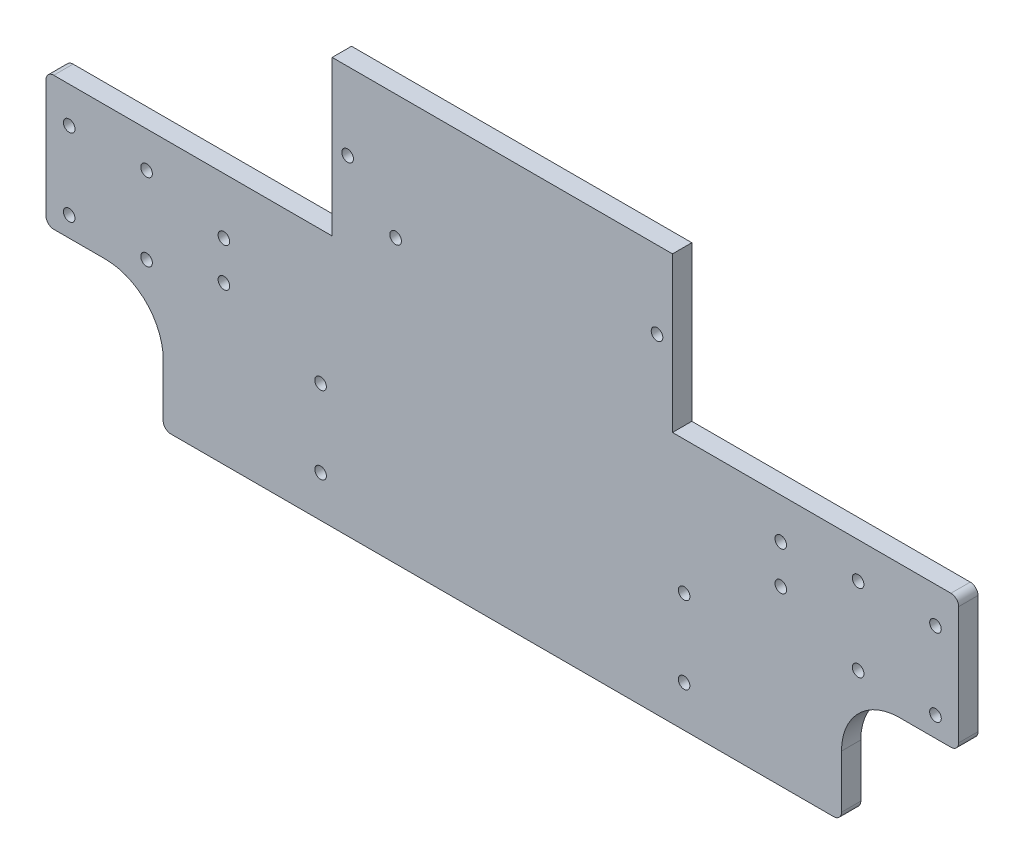
SolidWorks part; units mm, degrees
ref_plane "Plan de face" through (0, 0, 0) normal (0, 0, 1) x (1, 0, 0)
ref_plane "Plan de dessus" through (0, 0, 0) normal (0, 1, 0) x (1, 0, 0)
ref_plane "Plan de droite" through (0, 0, 0) normal (1, 0, 0) x (0, 0, -1)
sketch "Esquisse1" plane through (0, 0, 0) normal (0, 0, 1) x (1, 0, 0)
  line L0 (0, 0) -> (236, 0)
  line L1 (236, 0) -> (236, 65.2)
  line L2 (236, 65.2) -> (162, 65.2)
  line L3 (162, 65.2) -> (162, 105.2)
  line L4 (162, 105.2) -> (74, 105.2)
  line L5 (74, 105.2) -> (74, 65.2)
  line L6 (74, 65.2) -> (0, 65.2)
  line L7 (0, 65.2) -> (0, 0)
  line L8 (0, 30.7) -> (33, 30.7)
  line L10 (236, 30.7) -> (203, 30.7)
  line L12 (30.3, 30.7) -> (30.3, 0)
  line L13 (205.7, 30.7) -> (205.7, 0)
  circle A0 centre (15.3, 15.7) radius 15
  circle A1 centre (220.7, 15.7) radius 15
  dimension "D8" = 30
  dimension "D12" = 30
  dimension "D1" = 88
  dimension "D2" = 74
  dimension "D3" = 74
  dimension "D4" = 65.2
  dimension "D6" = 30.7
  dimension "D7" = 15.7
  dimension "D9" = 43.7
  dimension "D10" = 33
  dimension "D11" = 15.7
  dimension "D13" = 40
  dimension "D14" = 65.2
  dimension "D28" = 15
  dimension "D30" = 15
  dimension "D43" = 30.7
extrude "Boss.-Extru.1" add sketch "Esquisse1" along normal blind 5 contours L10 L1 L2 L3 L4 L5 L6 L7 L8 L0 | A0 L12 L8 | A1 L10 L13 region at (118, 45.344, 0) region at (26.9495, 27.3495, 0) region at (209.0505, 27.3495, 0)
fillet "Congé1" radius 2 6 edges at (0, 65.2, 2.5) (0, 30.7, 2.5) (30.3, 0, 2.5) (205.7, 0, 2.5) (236, 30.7, 2.5) (236, 65.2, 2.5)
sketch "Esquisse2" plane through (0, 0, 0) normal (0, 0, -1) x (-1, 0, 0)
  circle A0 centre (-165, 30.7) radius 1.5
  circle A1 centre (-165, 10.7) radius 1.5
  circle A2 centre (-71, 30.7) radius 1.5
  circle A3 centre (-71, 10.7) radius 1.5
  circle A4 centre (-158, 85.2) radius 1.5
  circle A5 centre (-78, 85.2) radius 1.5
  circle A6 centre (-26, 55.9) radius 1.5
  circle A7 centre (-26, 35.9) radius 1.5
  circle A8 centre (-6, 35.9) radius 1.5
  circle A9 centre (-6, 55.9) radius 1.5
  circle A10 centre (-230, 55.9) radius 1.5
  circle A11 centre (-230, 35.9) radius 1.5
  circle A12 centre (-210, 35.9) radius 1.5
  circle A13 centre (-210, 55.9) radius 1.5
  dimension "D1" = 3
  dimension "D2" = 3
  dimension "D3" = 3
  dimension "D4" = 3
  dimension "D5" = 3
  dimension "D6" = 3
  dimension "D7" = 3
  dimension "D8" = 3
  dimension "D9" = 3
  dimension "D10" = 3
  dimension "D11" = 3
  dimension "D12" = 3
  dimension "D13" = 3
  dimension "D14" = 3
extrude "Enlèv. mat.-Extru.1" cut sketch "Esquisse2" against normal through all
sketch "Esquisse3" plane through (0, 0, 0) normal (0, 0, -1) x (-1, 0, 0)
  circle A0 centre (-46, 50.7) radius 1.5
  circle A1 centre (-46, 40.7) radius 1.5
  circle A2 centre (-190, 44.7) radius 1.5
  circle A3 centre (-190, 54.7) radius 1.5
  dimension "D1" = 3
  dimension "D2" = 3
  dimension "D3" = 3
  dimension "D4" = 3
extrude "Enlèv. mat.-Extru.2" cut sketch "Esquisse3" against normal through all
sketch "Esquisse4" plane through (0, 0, 0) normal (0, 0, -1) x (-1, 0, 0)
  line L0 (-162, 105.2) -> (-74, 105.2) construction
  circle A0 centre (-90.4, 73) radius 1.5
  circle A1 centre (-138, 125.2) radius 1.5 construction
  dimension "D1" = 3
  dimension "D2" = 32.2
  dimension "D3" = 47.6
extrude "Enlèv. mat.-Extru.3" cut sketch "Esquisse4" against normal through all
